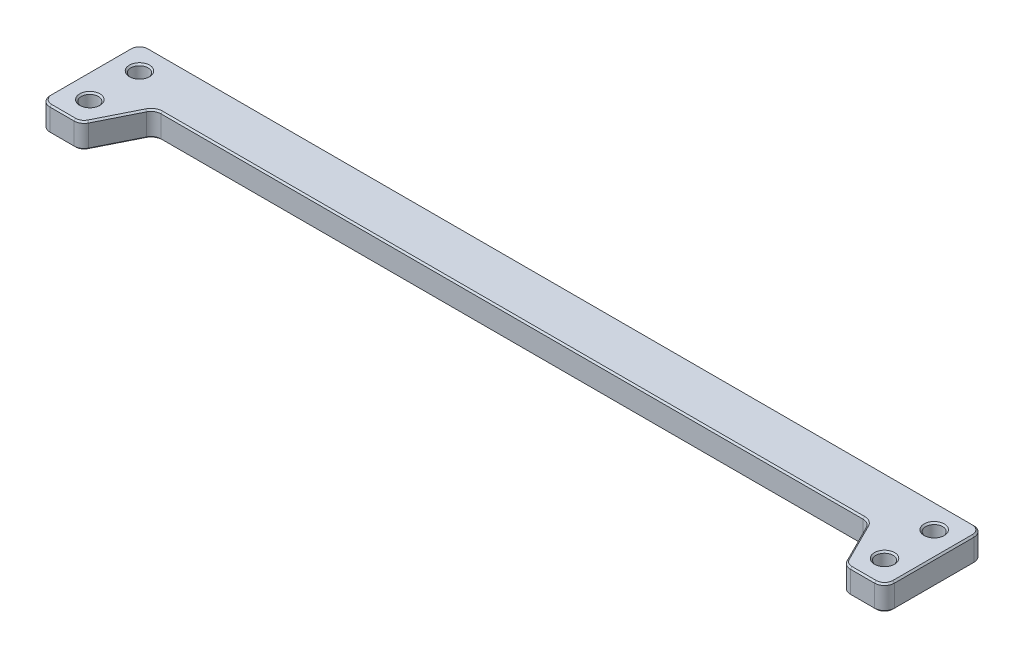
SolidWorks part; units mm, degrees
ref_plane "Front Plane" through (0, 0, 0) normal (0, 0, 1) x (1, 0, 0)
ref_plane "Top Plane" through (0, 0, 0) normal (0, 1, 0) x (1, 0, 0)
ref_plane "Right Plane" through (0, 0, 0) normal (1, 0, 0) x (0, 0, -1)
sketch "Sketch1" plane through (0, 0, 0) normal (0, 1, 0) x (1, 0, 0)
  line L0 (-3.81, 6.35) -> (207.01, 6.35)
  line L1 (209.55, 3.81) -> (209.55, -16.51)
  line L2 (207.01, -19.05) -> (200.8453, -19.05)
  line L3 (198.5734, -17.6459) -> (193.6275, -7.7541)
  line L4 (191.3557, -6.35) -> (11.8443, -6.35)
  line L5 (9.5725, -7.7541) -> (4.6266, -17.6459)
  line L6 (2.3547, -19.05) -> (-3.81, -19.05)
  line L7 (-6.35, -16.51) -> (-6.35, 3.81)
  circle A0 centre (0, 0) radius 2.1828
  circle A1 centre (0, -12.7) radius 2.1828
  circle A2 centre (203.2, 0) radius 2.1828
  circle A3 centre (203.2, -12.7) radius 2.1828
  arc A4 (207.01, 6.35) -> (209.55, 3.81) centre (207.01, 3.81) cw
  arc A5 (209.55, -16.51) -> (207.01, -19.05) centre (207.01, -16.51) cw
  arc A6 (200.8453, -19.05) -> (198.5734, -17.6459) centre (200.8453, -16.51) cw
  arc A7 (193.6275, -7.7541) -> (191.3557, -6.35) centre (191.3557, -8.89) ccw
  arc A8 (-3.81, 6.35) -> (-6.35, 3.81) centre (-3.81, 3.81) ccw
  arc A9 (11.8443, -6.35) -> (9.5725, -7.7541) centre (11.8443, -8.89) ccw
  arc A10 (4.6266, -17.6459) -> (2.3547, -19.05) centre (2.3547, -16.51) cw
  arc A11 (-3.81, -19.05) -> (-6.35, -16.51) centre (-3.81, -16.51) cw
  point P24 (199.2755, -19.05)
  point P27 (192.9255, -6.35)
  point P32 (10.2745, -6.35)
  point P35 (3.9245, -19.05)
  point P38 (-6.35, -19.05)
  dimension "D2" = 4.3656
  dimension "D3" = 4.3656
  dimension "D4" = 4.3656
  dimension "D5" = 4.3656
  dimension "D18" = 2.54
  dimension "D1" = 203.2
  dimension "D6" = 12.7
  dimension "D7" = 12.7
  dimension "D8" = 6.35
  dimension "D9" = 6.35
  dimension "D10" = 6.35
  dimension "D11" = 6.35
  dimension "D12" = 6.35
  dimension "D13" = 6.35
  dimension "D14" = 12.7
  dimension "D15" = 6.1647
  dimension "D16" = 6.35
  dimension "D17" = 6.1647
extrude "Boss-Extrude1" add sketch "Sketch1" along normal mid plane 6.35
chamfer "Chamfer1" distance 0.3969 angle 45 40 edges at (203.2, -3.175, 14.8828) (0, -3.175, 14.8828) (101.6, -3.175, -6.35) (-5.6061, -3.175, -5.6061) (-6.35, -3.175, 6.35) (-5.6061, -3.175, 18.3061) (-0.7276, -3.175, 19.05) (3.6901, -3.175, 18.6707) (7.0995, -3.175, 12.7) (10.509, -3.175, 6.7293) (101.6, -3.175, 6.35) (192.691, -3.175, 6.7293) (196.1005, -3.175, 12.7) (199.5099, -3.175, 18.6707) (203.9276, -3.175, 19.05) (208.8061, -3.175, 18.3061) (209.55, -3.175, 6.35) (208.8061, -3.175, -5.6061) (0, -3.175, 2.1828) (203.2, -3.175, 2.1828) (203.2, 3.175, 14.8828) (203.2, 3.175, 2.1828) (0, 3.175, 14.8828) (0, 3.175, 2.1828) (209.55, 3.175, 6.35) (208.8061, 3.175, 18.3061) (203.9276, 3.175, 19.05) (199.5099, 3.175, 18.6707) (196.1005, 3.175, 12.7) (192.691, 3.175, 6.7293) (101.6, 3.175, 6.35) (10.509, 3.175, 6.7293) (7.0995, 3.175, 12.7) (3.6901, 3.175, 18.6707) (-0.7276, 3.175, 19.05) (-5.6061, 3.175, 18.3061) (-6.35, 3.175, 6.35) (-5.6061, 3.175, -5.6061) (101.6, 3.175, -6.35) (208.8061, 3.175, -5.6061)
